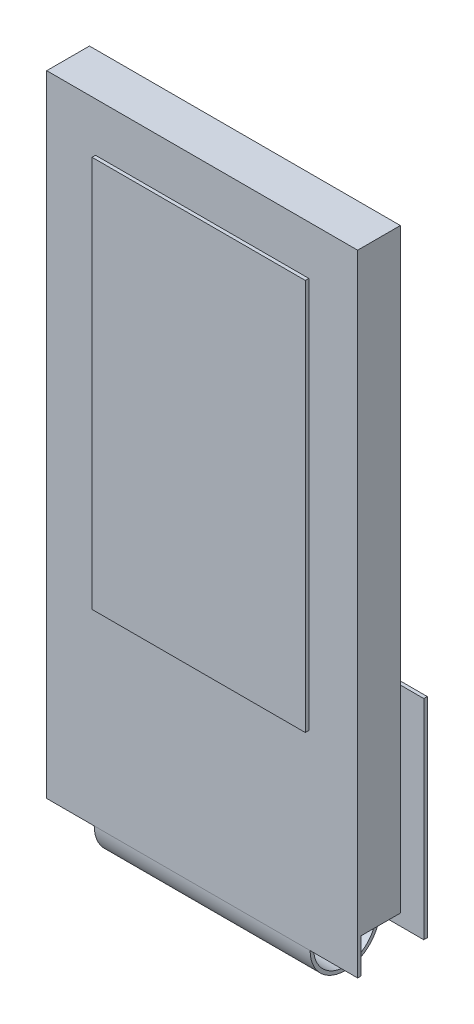
SolidWorks part; units mm, degrees
ref_plane "Plan de face" through (0, 0, 0) normal (0, 0, 1) x (1, 0, 0)
ref_plane "Plan de dessus" through (0, 0, 0) normal (0, 1, 0) x (1, 0, 0)
ref_plane "Plan de droite" through (0, 0, 0) normal (1, 0, 0) x (0, 0, -1)
sketch "Esquisse1" plane through (0, 0, 0) normal (0, 0, 1) x (1, 0, 0)
  line L1 (-4.464, -8.55) -> (4.464, -8.55)
  line L2 (-4.464, -8.55) -> (-4.464, 8.55)
  line L3 (-4.464, 8.55) -> (4.464, 8.55)
  line L4 (4.464, -8.55) -> (4.464, 8.55)
  line L5 (-4.464, -8.55) -> (4.464, 8.55) construction
  line L6 (-4.464, 8.55) -> (4.464, -8.55) construction
  point P0 (0, 0)
  dimension "D1" = 8.928
  dimension "D2" = 17.1
extrude "Boss.-Extru.1" add sketch "Esquisse1" along normal blind 1.227
sketch "Esquisse2" plane through (0, 0, 1.227) normal (0, 0, 1) x (1, 0, 0)
  line L0 (-4.464, -5.5) -> (4.464, -5.5) construction
  line L1 (-4.464, 8.55) -> (-4.464, -8.55) construction
  line L2 (4.464, -8.55) -> (4.464, 8.55) construction
  line L3 (4.464, 8.55) -> (-4.464, 8.55) construction
  line L4 (-4.464, 8.55) -> (4.464, -5.5) construction
  line L6 (-3.062, -4.097) -> (3.062, -4.097)
  line L7 (-3.062, -4.097) -> (-3.062, 7.147)
  line L8 (-3.062, 7.147) -> (3.062, 7.147)
  line L9 (3.062, -4.097) -> (3.062, 7.147)
  line L10 (-3.062, -4.097) -> (3.062, 7.147) construction
  line L11 (-3.062, 7.147) -> (3.062, -4.097) construction
  point P9 (0, 1.525)
  dimension "D1" = 14.05
  dimension "D2" = 6.124
  dimension "D3" = 11.244
extrude "Boss.-Extru.2" add sketch "Esquisse2" along normal blind 0.1
ref_plane "Plan1" through (0, 1.525, 0) normal (0, -1, 0) x (-1, 0, 0)
ref_plane "Plan2" through (0, 0, 0) normal (-1, 0, 0) x (0, 1, 0)
sketch "Esquisse4" plane through (4.464, 0, 0) normal (1, 0, 0) x (0, 0, -1)
  line L0 (-1.227, -8.55) -> (-1.227, -9.55)
  line L1 (0.773, -9.55) -> (0.773, -3.55)
  line L2 (0.773, -3.55) -> (0.673, -3.55)
  line L3 (0.673, -3.55) -> (0.673, -9.55)
  line L4 (-1.127, -9.55) -> (-1.127, -8.55)
  line L5 (-1.227, -8.55) -> (0, -8.55) construction
  line L6 (-1.127, -8.55) -> (-1.227, -8.55)
  arc A0 (-1.227, -9.55) -> (0.773, -9.55) centre (-0.227, -9.55) ccw
  arc A1 (0.673, -9.55) -> (-1.127, -9.55) centre (-0.227, -9.55) cw
  dimension "D2" = 1
  dimension "D4" = 1
  dimension "D1" = 0.1
  dimension "D3" = 6
extrude "Boss.-Extru.4" add sketch "Esquisse4" against normal up to surface (8.928 mm away) up to face at (-4.464, 0, 0.6135)
sketch "Esquisse5" plane through (0, 0, 1.227) normal (0, 0, 1) x (1, 0, 0)
  line L1 (-4.464, -9.55) -> (4.464, -9.55) construction
  line L2 (3.1, -9.55) -> (3.1, -10.55)
  line L3 (-4.464, -10.55) -> (4.464, -10.55) construction
  line L5 (-3.1, -10.55) -> (-3.1, -9.55)
  line L6 (3.1, -10.55) -> (4.464, -10.55)
  line L7 (-4.464, -10.55) -> (-3.1, -10.55)
  line L8 (-4.464, -10.55) -> (-4.464, -9.55)
  line L9 (-4.464, -9.55) -> (-3.1, -9.55)
  line L10 (4.464, -10.55) -> (4.464, -9.55)
  line L11 (3.1, -9.55) -> (4.464, -9.55)
  line L12 (3.1, -9.55) -> (-3.1, -9.55) construction
  line L13 (0, -9.55) -> (0, -10.55) construction
  dimension "D1" = 6.2
extrude "Enlèv. mat.-Extru.1" cut sketch "Esquisse5" against normal up to next
